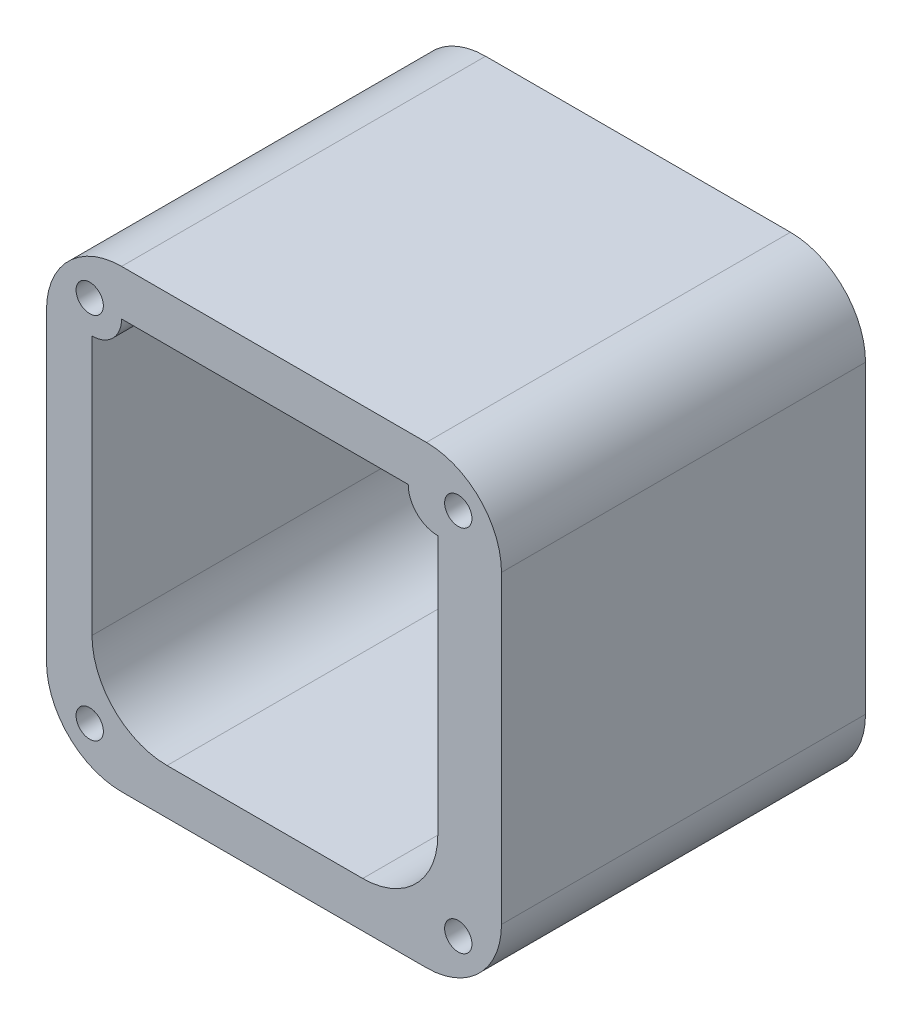
SolidWorks part; units mm, degrees
ref_plane "Front Plane" through (0, 0, 0) normal (0, 0, 1) x (1, 0, 0)
ref_plane "Top Plane" through (0, 0, 0) normal (0, 1, 0) x (1, 0, 0)
ref_plane "Right Plane" through (0, 0, 0) normal (1, 0, 0) x (0, 0, -1)
sketch "Sketch1" plane through (0, 0, 0) normal (0, 0, 1) x (1, 0, 0)
  line L1 (-5.461, -6.477) -> (5.461, -6.477)
  line L2 (-9.652, -2.286) -> (-9.652, 2.286)
  line L3 (-5.461, 6.477) -> (5.461, 6.477)
  line L4 (9.652, -2.286) -> (9.652, 2.286)
  line L5 (-9.652, -6.477) -> (9.652, 6.477) construction
  line L6 (-9.652, 6.477) -> (9.652, -6.477) construction
  line L7 (-5.461, -6.477) -> (13.208, -6.477)
  line L8 (-9.652, -2.286) -> (-9.652, 6.477)
  line L9 (-8.001, 16.383) -> (9.017, 16.383)
  line L10 (13.208, -4.826) -> (13.208, 12.192)
  line L12 (-9.652, 6.477) -> (-9.652, -2.286)
  line L14 (-12.192, 12.192) -> (-12.192, -4.826)
  line L15 (-8.001, -9.017) -> (9.017, -9.017)
  line L17 (-5.461, -6.477) -> (13.208, -6.477)
  arc A0 (-9.652, 2.286) -> (-5.461, 6.477) centre (-5.461, 2.286) cw
  arc A1 (5.461, -6.477) -> (9.652, -2.286) centre (5.461, -2.286) ccw
  arc A2 (9.652, 2.286) -> (5.461, 6.477) centre (5.461, 2.286) ccw
  arc A3 (-5.461, -6.477) -> (-9.652, -2.286) centre (-5.461, -2.286) cw
  arc A4 (-12.192, -4.826) -> (-8.001, -9.017) centre (-8.001, -4.826) ccw
  arc A5 (9.017, -9.017) -> (13.208, -4.826) centre (9.017, -4.826) ccw
  arc A6 (13.208, 12.192) -> (9.017, 16.383) centre (9.017, 12.192) ccw
  arc A7 (-12.192, 12.192) -> (-8.001, 16.383) centre (-8.001, 12.192) cw
  point P0 (0, 0)
  point P33 (13.208, 16.383)
  dimension "D3" = 4.191
  dimension "D4" = 4.191
  dimension "D7" = 4.191
  dimension "D1" = 19.304
  dimension "D2" = 12.954
extrude "Boss-Extrude1" add sketch "Sketch1" along normal blind 20.32 contours L1 A3 L2 A0 L3 A2 L4 A1 L10 L9 L14 L15 region at (11.1263, -8.025, 0)
sketch "Sketch3" plane through (0, 0, 20.32) normal (0, 0, 1) x (1, 0, 0)
  line L0 (-8.001, 16.383) -> (-8.001, 13.843) construction
  line L1 (-9.652, 12.192) -> (-12.192, 12.192) construction
  line L2 (-12.192, 12.192) -> (-12.192, -4.826) construction
  line L3 (-12.192, -4.826) -> (-8.001, -4.826) construction
  line L4 (-8.001, -4.826) -> (-8.001, -9.017) construction
  line L5 (-9.779, -6.604) -> (-9.779, -4.826) construction
  line L6 (-9.779, -6.604) -> (-8.001, -6.604) construction
  line L7 (0, 0) -> (0, 16.383) construction
  line L8 (0.508, 16.383) -> (0.508, -4.5204) construction
  line L9 (-9.652, 0) -> (9.652, 0)
  line L10 (-12.192, 3.683) -> (13.208, 3.683) construction
  line L11 (13.208, -4.826) -> (13.208, 12.192) construction
  line L12 (-9.652, 0) -> (-9.652, 12.192)
  line L13 (-9.652, -2.286) -> (-9.652, 2.286) construction
  line L14 (9.652, 0) -> (9.652, 3.683)
  line L15 (9.652, -2.286) -> (9.652, 2.286) construction
  line L16 (-8.001, 16.383) -> (9.017, 16.383) construction
  line L17 (-8.001, 13.843) -> (8.001, 13.843)
  line L18 (9.652, 0) -> (9.652, 12.192)
  arc A0 (-8.001, 16.383) -> (-12.192, 12.192) centre (-8.001, 12.192) ccw construction
  circle A1 centre (-9.779, -6.604) radius 0.762
  circle A2 centre (-9.779, 13.97) radius 0.762
  arc A5 (-9.652, 12.192) -> (-8.001, 13.843) centre (-9.652, 13.843) ccw
  arc A6 (9.652, 12.192) -> (8.001, 13.843) centre (9.652, 13.843) cw
  circle A7 centre (10.795, -6.604) radius 0.762
  circle A8 centre (10.795, 13.97) radius 0.762
  point P33 (0, 13.843)
  point P48 (0.508, 13.843)
  arc M20 (-9.652, 2.286) -> (-5.461, 6.477) centre (-5.461, 2.286) cw
  line M21 (-5.461, 6.477) -> (5.461, 6.477)
  arc M22 (5.461, 6.477) -> (9.652, 2.286) centre (5.461, 2.286) cw
  dimension "D1" = 1.524
  dimension "D2" = 1.778
  dimension "D3" = 1.778
extrude "Cut-Extrude1" cut sketch "Sketch3" against normal blind 17.78 contours L18 A6 L17 A5 L12 L14 M20 M21 M22 region at (0, 9.8328, 20.32)
extrude "Cut-Extrude2" cut sketch "Sketch3<6>" against normal blind 13.97 contours A2
sketch "Sketch3<6>" plane through (0, 0, 20.32) normal (0, 0, 1) x (1, 0, 0) same geometry as "Sketch3"
extrude "Cut-Extrude3" cut sketch "Sketch3<7>" against normal blind 13.97 contours A8
sketch "Sketch3<7>" plane through (0, 0, 20.32) normal (0, 0, 1) x (1, 0, 0) same geometry as "Sketch3"
extrude "Cut-Extrude4" cut sketch "Sketch3<8>" against normal blind 13.97 contours A7
sketch "Sketch3<8>" plane through (0, 0, 20.32) normal (0, 0, 1) x (1, 0, 0) same geometry as "Sketch3"
extrude "Cut-Extrude5" cut sketch "Sketch3<9>" against normal blind 13.97 contours A1
sketch "Sketch3<9>" plane through (0, 0, 20.32) normal (0, 0, 1) x (1, 0, 0) same geometry as "Sketch3"
